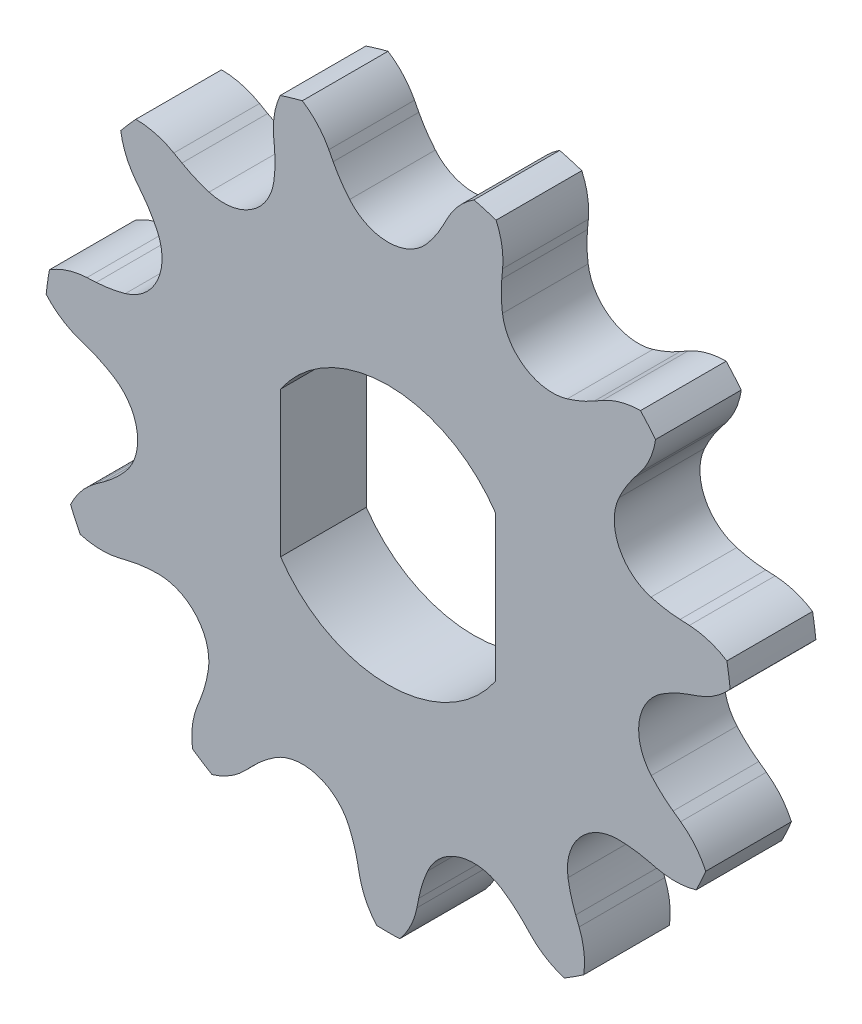
SolidWorks part; units mm, degrees
ref_plane "Plan de face" through (0, 0, 0) normal (0, 0, 1) x (1, 0, 0)
ref_plane "Plan de dessus" through (0, 0, 0) normal (0, 1, 0) x (1, 0, 0)
ref_plane "Plan de droite" through (0, 0, 0) normal (1, 0, 0) x (0, 0, -1)
sketch "Master Sk" plane through (0, 0, 0) normal (0, 0, 1) x (1, 0, 0)
  line L0 (0, 0) -> (0, 14.1979) construction
  line L1 (0, 0) -> (-7.6759, 11.944) construction
  line L2 (0, 14.1979) -> (-7.6759, 11.944) construction
  line L3 (0, 14.1979) -> (-2.3617, 14.1979) construction
  line L4 (0, 14.1979) -> (-1.7971, 12.6655) construction
  line L5 (0, 14.1979) -> (2.8611, 16.6375) construction
  line L6 (2.8611, 16.6375) -> (-2.5668, 13.8065) construction
  line L7 (-3.838, 13.0709) -> (-4.6654, 15.8888) construction
  line L8 (-2.5668, 13.8065) -> (-3.7753, 16.1235) construction
  line L9 (0, 14.1979) -> (-6.3135, 12.3441) construction
  line L10 (-6.3135, 12.3441) -> (-2.7684, 14.1931) construction
  line L11 (-5.3051, 13.0025) -> (-5.5411, 15.605) construction
  line L12 (-5.3051, 13.0025) -> (-5.3444, 13.4367)
  line L13 (-2.5668, 13.8065) -> (-2.7684, 14.1931)
  circle A2 centre (0, 14.1979) radius 2.35 construction
  circle A6 centre (0, 14.1979) radius 2.3618 construction
  arc A7 (0, 11.8361) -> (-1.7971, 12.6655) centre (0, 14.1979) cw
  arc A8 (-2.5668, 13.8065) -> (-1.7971, 12.6655) centre (2.8611, 16.6375) ccw
  circle A9 centre (0, 0) radius 16.5596 construction
  circle A10 centre (-6.3135, 12.3441) radius 3.9983 construction
  circle A11 centre (0, 14.1979) radius 3.9983 construction
  arc A12 (-5.3051, 13.0025) -> (-5.3356, 11.6264) centre (-11.4018, 12.4496) cw
  arc A13 (-6.3991, 9.9572) -> (-5.3356, 11.6264) centre (-7.6759, 11.944) ccw
  arc A14 (0, 11.8361) -> (-6.3991, 9.9572) centre (0, 0) ccw
  arc A15 (-4.6654, 15.8888) -> (-2.7684, 14.1931) centre (-5.9654, 12.5256) cw
  arc A16 (-4.6654, 15.8888) -> (-5.3444, 13.4367) centre (-1.7535, 13.7623) ccw
  arc A17 (-8.0031, 8.7203) -> (2.9228, 11.4696) centre (0, 0) ccw construction
  arc A18 (-6.3991, 9.9572) -> (-8.0031, 8.7203) centre (0, 0) ccw construction
  arc A19 (2.9228, 11.4696) -> (0, 11.8361) centre (0, 0) ccw construction
  dimension "D3" = 4.7
  dimension "D4" = 4.7235
  dimension "D9" = 6.1217
  dimension "D1" = 8
  dimension "D2" = 32.727
  dimension "D5" = 40.455
  dimension "D6" = 3.76
  dimension "D7" = 12.909
  dimension "D8" = 6.1217
  dimension "D10" = 6.58
sketch "Esquisse2" plane through (0, 0, 0) normal (0, 0, 1) x (1, 0, 0)
  circle A1 centre (0, 0) radius 11.8361
  arc A2 (-8.0031, 8.7203) -> (2.9228, 11.4696) centre (0, 0) ccw construction
extrude "Boss.-Extru.1" add sketch "Esquisse2" along normal blind 4
sketch "Esquisse3" plane through (0, 0, 4) normal (0, 0, 1) x (1, 0, 0)
  line L2 (-5.3444, 13.4367) -> (-5.3051, 13.0025)
  line L3 (-2.5668, 13.8065) -> (-2.7684, 14.1931)
  line L4 (-5.3444, 13.4367) -> (-5.3051, 13.0025)
  line L5 (-2.5668, 13.8065) -> (-2.7684, 14.1931)
  arc A7 (-4.6654, 15.8888) -> (-5.3444, 13.4367) centre (-1.7535, 13.7623) ccw
  arc A8 (-2.7684, 14.1931) -> (-4.6654, 15.8888) centre (-5.9654, 12.5256) ccw
  arc A9 (-2.5668, 13.8065) -> (-1.7971, 12.6655) centre (2.8611, 16.6375) ccw
  arc A10 (-1.7971, 12.6655) -> (0, 11.8361) centre (0, 14.1979) ccw
  arc A11 (0, 11.8361) -> (-6.3991, 9.9572) centre (0, 0) ccw
  arc A12 (-6.3991, 9.9572) -> (-5.3356, 11.6264) centre (-7.6759, 11.944) ccw
  arc A13 (-5.3356, 11.6264) -> (-5.3051, 13.0025) centre (-11.4018, 12.4496) ccw
  arc A14 (-4.6654, 15.8888) -> (-5.3444, 13.4367) centre (-1.7535, 13.7623) ccw
  arc A15 (-2.7684, 14.1931) -> (-4.6654, 15.8888) centre (-5.9654, 12.5256) ccw
  arc A16 (-2.5668, 13.8065) -> (-1.7971, 12.6655) centre (2.8611, 16.6375) ccw
  arc A17 (-1.7971, 12.6655) -> (0, 11.8361) centre (0, 14.1979) ccw
  arc A18 (0, 11.8361) -> (-6.3991, 9.9572) centre (0, 0) ccw
  arc A19 (-6.3991, 9.9572) -> (-5.3356, 11.6264) centre (-7.6759, 11.944) ccw
  arc A20 (-5.3356, 11.6264) -> (-5.3051, 13.0025) centre (-11.4018, 12.4496) ccw
  dimension "D1" = 0
extrude "Boss.-Extru.2" add sketch "Esquisse3" against normal up to surface (4 mm away) up to face at (11.8361, 0, 0)
ref_axis "Axe1" through (0, 0, 4) along (0, 0, -1)
pattern_circular "Répétition circulaire1" count 11 over 360 about axis through (0, 0, 4) along (0, 0, -1) of "Boss.-Extru.2"
sketch "Esquisse4" plane through (0, 0, 4) normal (0, 0, 1) x (1, 0, 0)
  circle A0 centre (0, 0) radius 27
  dimension "D1" = 54
sketch "Esquisse5" plane through (0, 0, 0) normal (0, 0, -1) x (-1, 0, 0)
  line L0 (0, 0) -> (0, 64.8709) construction
  line L1 (0, 0) -> (58.7515, 58.7515) construction
  line L2 (6, 41.5692) -> (6, 58.983)
  line L3 (41.5692, 6) -> (58.983, 6)
  arc A0 (9.7209, 36.7356) -> (36.7356, 9.7209) centre (0, 0) cw
  arc A1 (11.9167, 63.8983) -> (63.8983, 11.9167) centre (0, 0) cw
  arc A2 (41.5692, 6) -> (36.7356, 9.7209) centre (41.5692, 11) cw
  arc A3 (0, 65) -> (6, 64.7225) centre (0, 0) cw construction
  arc A4 (0, 65) -> (45.9619, 45.9619) centre (0, 0) cw construction
  arc A5 (0, 38) -> (6, 37.5233) centre (0, 0) cw construction
  arc A6 (0, 38) -> (26.8701, 26.8701) centre (0, 0) cw construction
  arc A7 (58.983, 6) -> (63.8983, 11.9167) centre (58.983, 11) ccw
  arc A8 (6, 58.983) -> (11.9167, 63.8983) centre (11, 58.983) cw
  arc A9 (6, 41.5692) -> (9.7209, 36.7356) centre (11, 41.5692) ccw
  point P15 (37.5233, 6)
  point P18 (64.7225, 6)
  dimension "D2" = 38
  dimension "D5" = 5
  dimension "D1" = 45
  dimension "D4" = 12
  dimension "D3" = 27
sketch "Esquisse6" plane through (0, 0, 0) normal (0, 0, -1) x (-1, 0, 0)
  circle A0 centre (0, 0) radius 16.0596
  circle A1 centre (0, 0) radius 16.5596
  dimension "D1" = 0.5
extrude "Enlèv. mat.-Extru.3" cut sketch "Esquisse6" against normal through all
sketch "Sketch1" plane through (0, 0, 4) normal (0, 0, 1) x (1, 0, 0)
  line L2 (-5.02, 3.39) -> (-5.02, -3.39)
  line L4 (5.02, 3.39) -> (5.02, -3.39)
  line L5 (-5.02, 3.39) -> (5.02, -3.39) construction
  line L6 (-5.02, -3.39) -> (5.02, 3.39) construction
  arc A0 (-5.02, -3.39) -> (5.02, -3.39) centre (0, 0) ccw
  arc A1 (5.02, 3.39) -> (-5.02, 3.39) centre (0, 0) ccw
  point P0 (0, 0)
  dimension "D1" = 10.04
  dimension "D2" = 6.78
extrude "Cut-Extrude1" cut sketch "Sketch1" against normal blind 10
equation "\"pitch\"= 8'Pas"
equation "\"Z\" = 11'Nb de dents"
equation "\"Roller\"= 4.7'Roller diam"
equation "\"D1@Master Sk\" = \"pitch\""
equation "\"D2@Master Sk\" = 360 / \"Z\""
equation "\"D3@Master Sk\" = \"Roller\""
equation "\"HubSeat\"= 1.005 * \"Roller\"'HubSeat"
equation "\"D4@Master Sk\" = \"HubSeat\""
equation "\"A\"= 35 + ( 60 / \"Z\" )'Cote A"
equation "\"D5@Master Sk\" = \"A\""
equation "\"R1\"= \"HubSeat\" / 2'Demi HubSeat"
equation "\"oc\"= \"Roller\" * 0.8'ref oc"
equation "\"D6@Master Sk\" = \"oc\""
equation "\"R2\"= 18 - ( 56 / \"Z\" )'ref r2"
equation "\"D7@Master Sk\" = \"R2\""
equation "\"D8@Master Sk\" = \"R1\" + \"oc\""
equation "\"D10@Master Sk\" = \"Roller\" * 1.4"
equation "\"R2_2\"= \"R1\" + \"oc\""
equation "\"D9@Master Sk\" = \"R2_2\""
equation "\"Ep\"= 4'épaisseur pignon"
equation "\"D1@Boss.-Extru.1\"=\"Ep\""
equation "\"D1@Répétition circulaire1\"=\"Z\""
